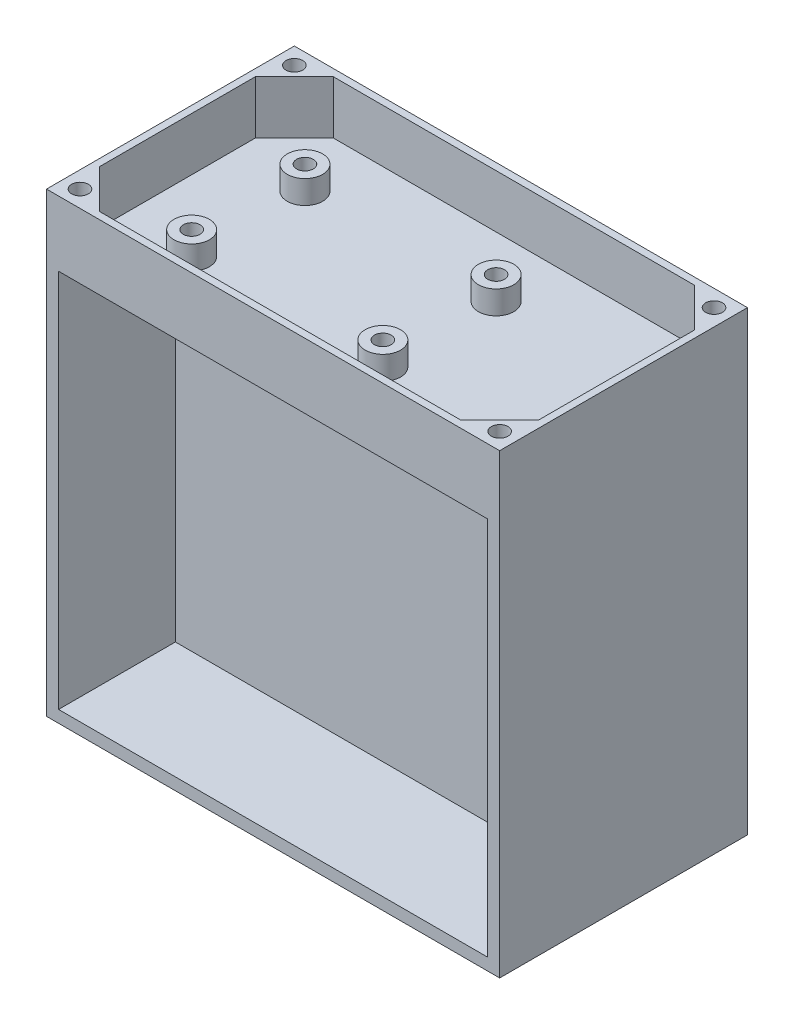
SolidWorks part; units mm, degrees
ref_plane "Front Plane" through (0, 0, 0) normal (0, 0, 1) x (1, 0, 0)
ref_plane "Top Plane" through (0, 0, 0) normal (0, 1, 0) x (1, 0, 0)
ref_plane "Right Plane" through (0, 0, 0) normal (1, 0, 0) x (0, 0, -1)
sketch "Sketch1" plane through (0, 0, 0) normal (0, 1, 0) x (1, 0, 0)
  line L1 (0, 0) -> (81.28, 0)
  line L2 (0, 0) -> (0, 44.45)
  line L3 (0, 44.45) -> (81.28, 44.45)
  line L4 (81.28, 0) -> (81.28, 44.45)
  dimension "D1" = 81.28
  dimension "D2" = 44.45
extrude "Boss-Extrude1" add sketch "Sketch1" along normal blind 72.39
sketch "Sketch2" plane through (0, 0, 0) normal (0, 0, 1) x (1, 0, 0)
  line L0 (0, 72.39) -> (0, 0) construction
  line L1 (2.159, 2.159) -> (79.121, 2.159)
  line L2 (2.159, 2.159) -> (2.159, 70.231)
  line L3 (2.159, 70.231) -> (79.121, 70.231)
  line L4 (79.121, 2.159) -> (79.121, 70.231)
  line L5 (81.28, 72.39) -> (81.28, 0) construction
  line L6 (0, 0) -> (81.28, 0) construction
  line L7 (0, 72.39) -> (81.28, 72.39) construction
  dimension "D1" = 2.159
  dimension "D2" = 2.159
  dimension "D3" = 2.159
  dimension "D4" = 2.159
extrude "Cut-Extrude1" cut sketch "Sketch2" against normal blind 20.955
sketch "Sketch3" plane through (0, 0, -44.45) normal (0, 0, -1) x (-1, 0, 0)
  line L1 (-79.121, 2.159) -> (-2.159, 2.159)
  line L2 (-79.121, 2.159) -> (-79.121, 70.231)
  line L3 (-79.121, 70.231) -> (-2.159, 70.231)
  line L4 (-2.159, 2.159) -> (-2.159, 70.231)
  line L8 (0, 72.39) -> (0, 0) construction
  line L9 (-81.28, 0) -> (0, 0) construction
  line L10 (-81.28, 72.39) -> (-81.28, 0) construction
  line L11 (-81.28, 72.39) -> (0, 72.39) construction
  dimension "D1" = 2.159
  dimension "D2" = 2.159
  dimension "D3" = 2.159
  dimension "D4" = 2.159
extrude "Cut-Extrude2" cut sketch "Sketch3" against normal blind 20.955
sketch "Sketch4" plane through (0, 72.39, 0) normal (0, 1, 0) x (1, 0, 0)
  line L1 (0, 0) -> (81.28, 0)
  line L2 (0, 0) -> (0, 44.45)
  line L3 (0, 44.45) -> (81.28, 44.45)
  line L4 (81.28, 0) -> (81.28, 44.45)
  line L5 (1.27, 1.27) -> (80.01, 1.27)
  line L6 (1.27, 1.27) -> (1.27, 43.18)
  line L7 (1.27, 43.18) -> (80.01, 43.18)
  line L8 (80.01, 1.27) -> (80.01, 43.18)
  dimension "D1" = 1.27
  dimension "D2" = 1.27
  dimension "D3" = 1.27
  dimension "D4" = 1.27
extrude "Boss-Extrude2" add sketch "Sketch4" along normal blind 9.525
sketch "Sketch5" plane through (0, 72.39, 0) normal (0, 1, 0) x (1, 0, 0)
  line L0 (0, 0) -> (81.28, 0) construction
  line L2 (1.27, 43.18) -> (1.27, 1.27) construction
  circle A0 centre (13.97, 12.065) radius 3.175
  circle A1 centre (13.97, 12.065) radius 1.5
  circle A2 centre (13.97, 32.385) radius 3.175
  circle A3 centre (13.97, 32.385) radius 1.5
  circle A4 centre (48.26, 32.385) radius 3.175
  circle A5 centre (48.26, 32.385) radius 1.5
  circle A6 centre (48.26, 12.065) radius 3.175
  circle A7 centre (48.26, 12.065) radius 1.5
  dimension "D4" = 6.35
  dimension "D5" = 6.35
  dimension "D6" = 6.35
  dimension "D7" = 6.35
  dimension "D8" = 3
  dimension "D9" = 3
  dimension "D10" = 3
  dimension "D11" = 3
  dimension "D1" = 20.32
  dimension "D2" = 12.065
  dimension "D3" = 34.29
  dimension "D12" = 12.7
extrude "Boss-Extrude3" add sketch "Sketch5" along normal blind 4.191
extrude "Cut-Extrude3" cut sketch "Sketch5<2>" against normal up to next contours A1 | A3 | A5 | A7 region at (13.97, 72.39, -12.065) region at (13.97, 72.39, -32.385) region at (48.26, 72.39, -32.385) region at (48.26, 72.39, -12.065)
sketch "Sketch5<2>" plane through (0, 72.39, 0) normal (0, 1, 0) x (1, 0, 0) same geometry as "Sketch5"
chamfer "Chamfer1" distance 6.985 angle 45 4 edges at (80.01, 77.1525, -1.27) (80.01, 77.1525, -43.18) (1.27, 77.1525, -1.27) (1.27, 77.1525, -43.18)
sketch "Sketch6" plane through (0, 81.915, 0) normal (0, 1, 0) x (1, 0, 0)
  line L0 (0, 0) -> (81.28, 0) construction
  line L1 (81.28, 44.45) -> (0, 44.45) construction
  line L2 (81.28, 0) -> (81.28, 44.45) construction
  line L3 (0, 44.45) -> (0, 0) construction
  circle A0 centre (3, 3) radius 1.5
  circle A1 centre (3, 41.45) radius 1.5
  circle A2 centre (78.28, 41.45) radius 1.5
  circle A3 centre (78.28, 3) radius 1.5
  dimension "D1" = 3
  dimension "D2" = 3
  dimension "D3" = 3
  dimension "D4" = 3
  dimension "D5" = 3
  dimension "D6" = 3
  dimension "D7" = 3
  dimension "D8" = 3
extrude "Cut-Extrude4" cut sketch "Sketch6" against normal up to surface (11.684 mm away) up to face at (48.26, 70.231, -10.565)
